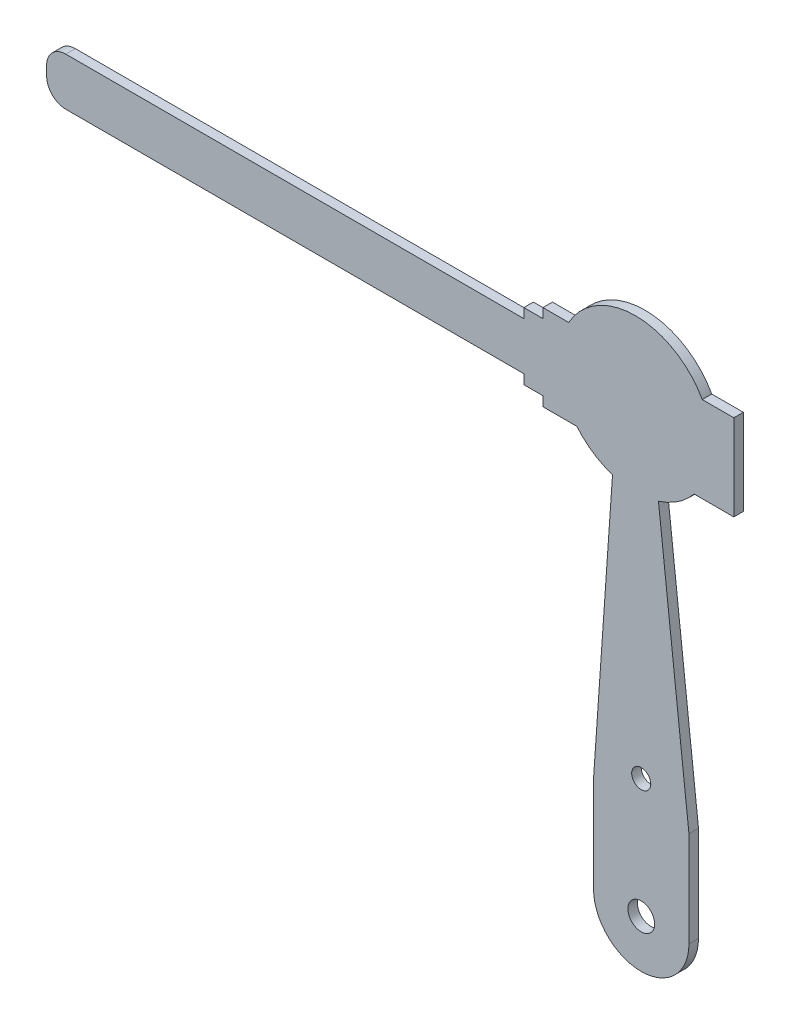
SolidWorks part; units mm, degrees
ref_plane "Alzado" through (0, 0, 0) normal (0, 0, 1) x (1, 0, 0)
ref_plane "Planta" through (0, 0, 0) normal (0, 1, 0) x (1, 0, 0)
ref_plane "Vista lateral" through (0, 0, 0) normal (1, 0, 0) x (0, 0, -1)
sketch "Model" plane through (0, 0, 0) normal (0, 0, 1) x (1, 0, 0)
  line L0 (40.206, -5.7616) -> (42.1979, 22.8197)
  line L1 (50.206, -15.7616) -> (40.206, -15.7616) construction
  line L2 (50.206, -5.7616) -> (50.206, -15.7616)
  line L3 (50.206, -5.7616) -> (47.0109, 22.8197)
  line L4 (54.9064, 25.3339) -> (50.7552, 25.3339)
  line L5 (34.9064, 25.3339) -> (38.4535, 25.3339)
  line L6 (34.9064, 25.3339) -> (34.9064, 26.3339)
  line L7 (34.9064, 26.3339) -> (32.9064, 26.3339)
  line L8 (40.206, -5.7616) -> (40.206, -15.7616)
  line L9 (32.9064, 26.3339) -> (32.9064, 27.3339)
  line L10 (32.9064, 27.3339) -> (-15.0936, 27.3339)
  line L11 (-17.0936, 29.3339) -> (-17.0936, 30.3339)
  line L12 (-15.0936, 32.3339) -> (32.9064, 32.3339)
  line L13 (32.9064, 32.3339) -> (32.9064, 33.3339)
  line L14 (32.9064, 33.3339) -> (34.9064, 33.3339)
  line L15 (45.206, -2.0116) -> (45.206, 22.9884) construction
  line L16 (47.706, 10.4884) -> (55.206, 10.4884) construction
  line L17 (34.9064, 33.3339) -> (34.9064, 34.3339)
  line L18 (51.5979, 34.3339) -> (54.9064, 34.3339)
  line L19 (54.9064, 34.3339) -> (54.9064, 25.3339)
  line L20 (34.9064, 34.3339) -> (37.6108, 34.3339)
  arc A0 (-17.0936, 29.3339) -> (-15.0936, 27.3339) centre (-15.0936, 29.3339) ccw
  arc A1 (40.206, -15.7616) -> (50.206, -15.7616) centre (45.206, -15.7616) ccw
  arc A2 (-15.0936, 32.3339) -> (-17.0936, 30.3339) centre (-15.0936, 30.3339) ccw
  arc A4 (42.1979, 22.8197) -> (38.4535, 25.3339) centre (44.6044, 30.4492) cw
  circle A5 centre (45.206, -15.7616) radius 1.4
  circle A6 centre (45.206, -3.2616) radius 1
  arc A7 (47.0109, 22.8197) -> (50.7552, 25.3339) centre (44.6044, 30.4492) ccw
  arc A15 (37.6108, 34.3339) -> (51.5979, 34.3339) centre (44.6044, 30.4492) cw
  dimension "D2" = 12.5
  dimension "D3" = 10
  dimension "D12" = 10
base flange "Brida base1" sketch "Model" thickness 1 reverse thickness direction no parameters "D1"=0.7366
sketch "Líneas de pliegue1" [suppressed] plane through (0, 0, 0) normal (0, 1, 0) x (1, 0, 0)
sketch "Cuadro delimitador1" [suppressed] plane through (0, 0, 0) normal (0, 1, 0) x (1, 0, 0)
sheet metal parameters "Chapa metálica1" thickness 1 parameters "D1"=0.7366
flat pattern "Chapa desplegada1" [suppressed]
sketch "Líneas de pliegue2" plane through (0, 0, 0) normal (0, 0, 1) x (1, 0, 0)
sketch3d "Cuadro delimitador2" [suppressed]
  line L0 (28.217, 38.9253, 0) -> (92.5492, -13.3086, 0) construction
  line L1 (-3.3025, 0.1053, 0) -> (61.0297, -52.1286, 0) construction
  line L2 (28.217, 38.9253, 0) -> (-3.3025, 0.1053, 0) construction
  line L3 (92.5492, -13.3086, 0) -> (61.0297, -52.1286, 0) construction
